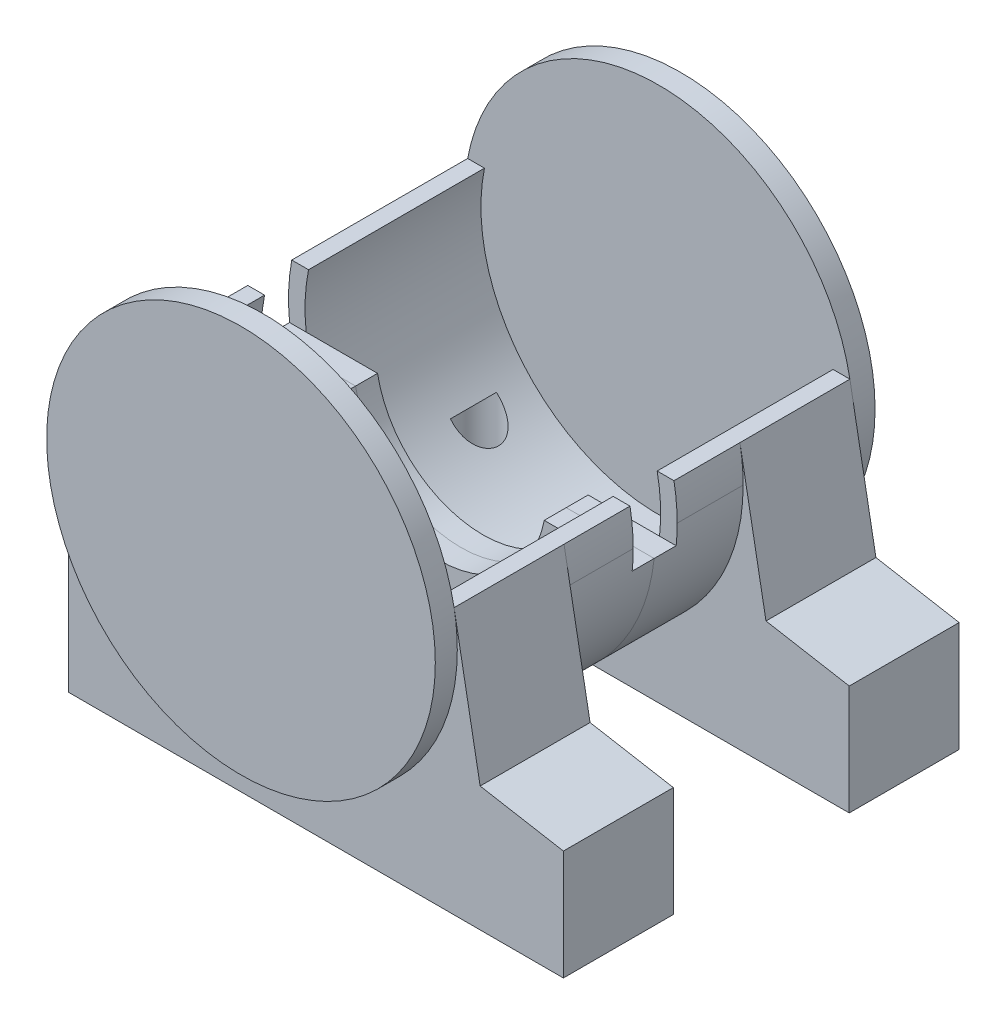
SolidWorks part; units mm, degrees
ref_plane "Front Plane" through (0, 0, 0) normal (0, 0, 1) x (1, 0, 0)
ref_plane "Top Plane" through (0, 0, 0) normal (0, 1, 0) x (1, 0, 0)
ref_plane "Right Plane" through (0, 0, 0) normal (1, 0, 0) x (0, 0, -1)
sketch "Sketch1" plane through (0, 0, 0) normal (0, 0, 1) x (1, 0, 0)
  line L0 (-17.3829, 3.2) -> (-15.8553, 3.2)
  line L1 (15.8553, 3.2) -> (17.3829, 3.2)
  circle A0 centre (0, 0) radius 16.175
  circle A1 centre (0, 0) radius 17.675
  dimension "D1" = 32.35
  dimension "D2" = 35.35
  dimension "D3" = 3.2
extrude "Boss-Extrude1" add sketch "Sketch1" against normal blind 2 contours A0 | L0 A1 L1 A0 | L1 A1 L0 A0 region at (0, 17.2984, 0) region at (-16.6191, 2.7895, 0) region at (0, 0, 0)
extrude "Boss-Extrude2" add sketch "Sketch1<4>" along normal blind 16 contours L0 A1 L1 A0 region at (-16.6191, 2.7895, 0)
sketch "Sketch1<4>" plane through (0, 0, 0) normal (0, 0, 1) x (1, 0, 0) same geometry as "Sketch1"
sketch "Sketch2" plane through (0, 0, 16) normal (0, 0, 1) x (1, 0, 0)
  line L0 (-17.5805, -1.825) -> (-9.5805, -1.825)
  line L1 (17.5805, -1.825) -> (9.5805, -1.825)
  circle A0 centre (0, 0) radius 17.675
  arc A1 (9.5805, -1.825) -> (-9.5805, -1.825) centre (0, 0) cw
  arc M4 (-17.3829, 3.2) -> (17.3829, 3.2) centre (0, 0) ccw
  arc M6 (15.8553, 3.2) -> (-15.8553, 3.2) centre (0, 0) cw
  dimension "D1" = 8
  dimension "D2" = 1.825
extrude "Boss-Extrude3" add sketch "Sketch2" along normal blind 2 contours L1 A1 L0 M6 | L1 L0 M4 M6 region at (-16.8261, -2.2107, 16) region at (-12.8261, -2.177, 16)
sketch "Sketch3" plane through (0, 0, 0) normal (0, 0, 1) x (1, 0, 0)
  line L3 (-17.675, -21.0022) -> (27.325, -21.0022)
  line L5 (27.325, -21.0022) -> (27.325, -11.0022)
  line L8 (-17.675, 0) -> (-17.675, -21.0022)
  line L10 (17.3829, 3.2) -> (19.7515, -9.6668)
  line L11 (19.7515, -9.6668) -> (27.325, -11.0022)
  arc A0 (-17.5805, -1.825) -> (17.5805, -1.825) centre (0, 0) ccw construction
  arc A1 (17.3829, 3.2) -> (-17.675, 0) centre (0, 0) cw
  arc A2 (17.3829, 3.2) -> (-17.3829, 3.2) centre (0, 0) ccw construction
  arc A3 (-17.3829, 3.2) -> (-17.5805, -1.825) centre (0, 0) ccw construction
  dimension "D1" = 45
  dimension "D2" = 21.0022
  dimension "D3" = 100
  dimension "D4" = 10
extrude "Boss-Extrude4" add sketch "Sketch3" along normal blind 10
sketch "Sketch5" plane through (0, -21.0022, 0) normal (0, -1, 0) x (1, 0, 0)
  line L0 (-11.675, 5) -> (21.325, 5) construction
  line L7 (-17.675, 10) -> (-17.675, 0) construction
  line L9 (-17.675, 0) -> (27.325, 0) construction
  circle A0 centre (-11.675, 5) radius 2.1
  circle A1 centre (21.325, 5) radius 2.1
  point P1 (-17.675, 5)
  point P16 (4.825, 0)
  point P17 (4.825, 5)
  dimension "D1" = 4.2
  dimension "D2" = 6
extrude "Cut-Extrude3" cut sketch "Sketch5" against normal blind 10 contours A0 | A1 region at (-11.675, -21.0022, 5) region at (21.325, -21.0022, 5)
ref_axis "Axis1" through (0, 0, 33.509) along (0, 0, -1)
mirror "Mirror1" about plane through (0, 0, 18) normal (0, 0, 1) of bodies 112
